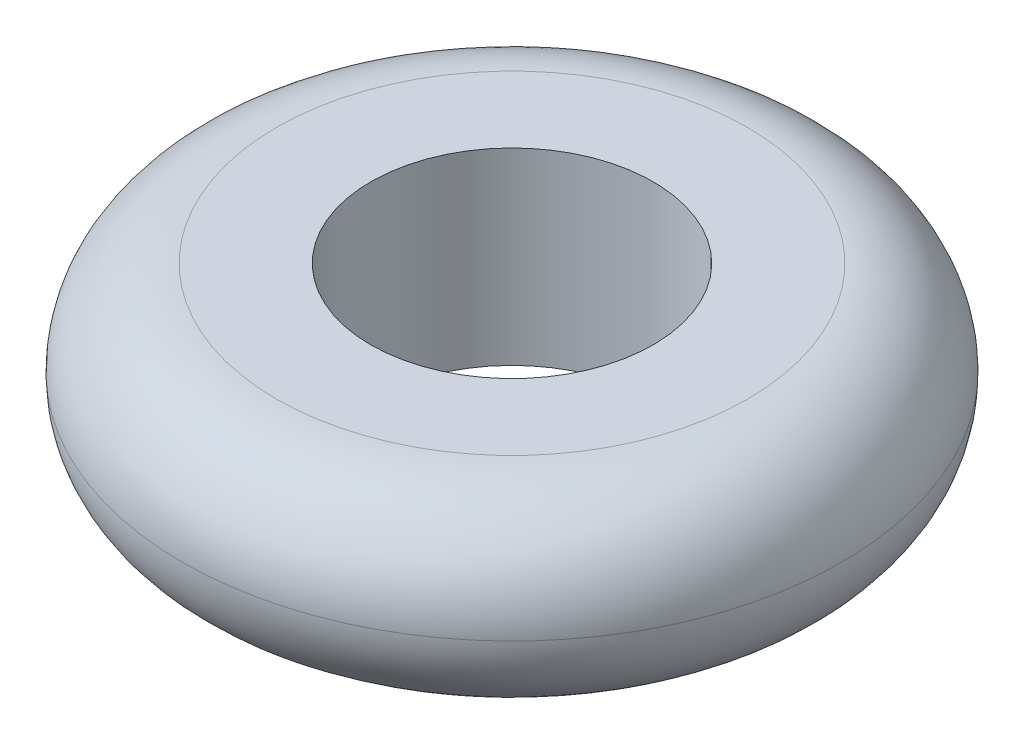
SolidWorks part; units mm, degrees
material "Rubber"
ref_plane "Front Plane" through (0, 0, 0) normal (0, 0, 1) x (1, 0, 0)
ref_plane "Top Plane" through (0, 0, 0) normal (0, 1, 0) x (1, 0, 0)
ref_plane "Right Plane" through (0, 0, 0) normal (1, 0, 0) x (0, 0, -1)
sketch "Sketch1" plane through (0, 0, 0) normal (0, 1, 0) x (1, 0, 0)
  circle A0 centre (0, 0.377) radius 0.75
  circle A1 centre (0, 0.377) radius 1.75
  dimension "D1" = 1
  dimension "D2" = 1.5
extrude "Boss-Extrude1" add sketch "Sketch1" along normal blind 1
fillet "Fillet1" radius 0.5 2 edges at (0, 0, 1.373) (0, 1, 1.373)
